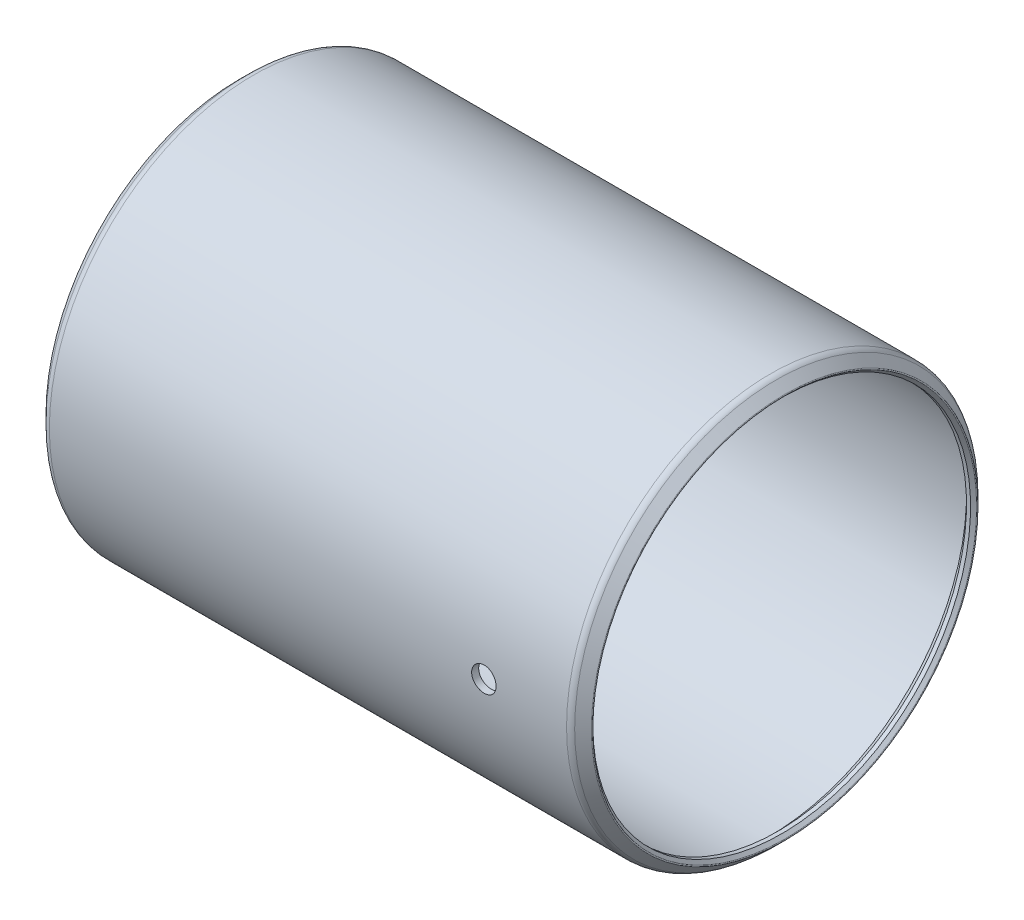
SolidWorks part; units mm, degrees
material "Cast Alloy Steel"
ref_plane "Front Plane" through (0, 0, 0) normal (0, 0, 1) x (1, 0, 0)
ref_plane "Top Plane" through (0, 0, 0) normal (0, 1, 0) x (1, 0, 0)
ref_plane "Right Plane" through (0, 0, 0) normal (1, 0, 0) x (0, 0, -1)
ref_plane "Plane1" through (68.961, 0, 0) normal (1, 0, 0) x (0, 0, -1)
sketch "Sketch1" plane through (0, 0, 0) normal (0, 0, 1) x (1, 0, 0)
  line L0 (-0.9191, 24.9094) -> (-0.5271, 24.5174)
  line L1 (-0.5271, 24.5174) -> (0, 24.5174)
  line L2 (0, 24.5174) -> (1.0541, 25.5714)
  line L3 (1.0541, 25.5714) -> (67.9069, 25.5714)
  line L4 (67.9069, 25.5714) -> (68.961, 24.5174)
  line L5 (68.961, 24.5174) -> (69.4881, 24.5174)
  line L6 (69.4881, 24.5174) -> (69.8801, 24.9094)
  line L7 (69.8801, 25.089) -> (68.792, 26.1771)
  line L8 (68.0466, 26.4858) -> (0.9144, 26.4858)
  line L9 (0.169, 26.1771) -> (-0.9191, 25.089)
  line L10 (68.961, 0) -> (0, 0) construction
  arc A0 (-0.9191, 25.089) -> (-0.9191, 24.9094) centre (-0.8293, 24.9992) ccw
  arc A1 (69.8801, 24.9094) -> (69.8801, 25.089) centre (69.7903, 24.9992) ccw
  arc A2 (68.792, 26.1771) -> (68.0466, 26.4858) centre (68.0466, 25.4317) ccw
  arc A3 (0.9144, 26.4858) -> (0.169, 26.1771) centre (0.9144, 25.4317) ccw
revolve "Revolve1" add sketch "Sketch1" angle 360 about L10 reverse direction yes
sketch "Sketch2" plane through (0, 0, 0) normal (0, 0, 1) x (1, 0, 0)
  circle A0 centre (57.3151, 0) radius 1.5875
extrude "Cut-Extrude1" cut sketch "Sketch2" along normal blind 26.4858
ref_plane "Plane2" through (34.4805, 0, 0) normal (1, 0, 0) x (0, 0, -1)
ref_plane "cp1 XY" through (34.4805, 0, 0) normal (1, 0, 0) x (0, 0, -1)
ref_plane "cp1 XZ" through (0, 26.4858, 0) normal (0, -1, 0) x (-1, 0, 0)
ref_plane "cp1 YZ" through (0, 0, 0) normal (0, 0, -1) x (-1, 0, 0)
ref_axis "cp1 X" through (34.4805, 26.4858, 80.9) along (0, 0, -1)
ref_axis "cp1 Y" through (34.4805, -50, 0) along (0, 1, 0)
ref_axis "cp1 Z" through (80.9, 26.4858, 0) along (-1, 0, 0)
sketch3d "cp1"
  point P0 (34.4805, 26.4858, 0)
ref_plane "cp2 XY" through (34.4805, 0, 0) normal (1, 0, 0) x (0, 0, -1)
ref_plane "cp2 XZ" through (0, 0, 0) normal (0, -1, 0) x (-1, 0, 0)
ref_plane "cp2 YZ" through (0, 0, -26.4858) normal (0, 0, -1) x (-1, 0, 0)
ref_axis "cp2 X" through (34.4805, 0, 80.9) along (0, 0, -1)
ref_axis "cp2 Y" through (34.4805, -50, -26.4858) along (0, 1, 0)
ref_axis "cp2 Z" through (80.9, 0, -26.4858) along (-1, 0, 0)
sketch3d "cp2"
  point P0 (34.4805, 0, -26.4858)
ref_plane "cp3 XY" through (34.4805, 0, 0) normal (1, 0, 0) x (0, 0, -1)
ref_plane "cp3 XZ" through (0, -26.4858, 0) normal (0, -1, 0) x (-1, 0, 0)
ref_plane "cp3 YZ" through (0, 0, 0) normal (0, 0, -1) x (-1, 0, 0)
ref_axis "cp3 X" through (34.4805, -26.4858, 80.9) along (0, 0, -1)
ref_axis "cp3 Y" through (34.4805, -50, 0) along (0, 1, 0)
ref_axis "cp3 Z" through (80.9, -26.4858, 0) along (-1, 0, 0)
sketch3d "cp3"
  point P0 (34.4805, -26.4858, 0)
ref_plane "cp4 XY" through (34.4805, 0, 0) normal (1, 0, 0) x (0, 0, -1)
ref_plane "cp4 XZ" through (0, 0, 0) normal (0, -1, 0) x (-1, 0, 0)
ref_plane "cp4 YZ" through (0, 0, 26.4858) normal (0, 0, -1) x (-1, 0, 0)
ref_axis "cp4 X" through (34.4805, 0, 80.9) along (0, 0, -1)
ref_axis "cp4 Y" through (34.4805, -50, 26.4858) along (0, 1, 0)
ref_axis "cp4 Z" through (80.9, 0, 26.4858) along (-1, 0, 0)
sketch3d "cp4"
  point P0 (34.4805, 0, 26.4858)
ref_plane "tube_front XY" through (0, 0, 0) normal (1, 0, 0) x (0, 0, -1)
ref_plane "tube_front XZ" through (0, 0, 0) normal (0, -1, 0) x (-1, 0, 0)
ref_plane "tube_front YZ" through (0, 0, 0) normal (0, 0, -1) x (-1, 0, 0)
ref_axis "tube_front X" through (0, 0, 80.9) along (0, 0, -1)
ref_axis "tube_front Y" through (0, -50, 0) along (0, 1, 0)
ref_axis "tube_front Z" through (80.9, 0, 0) along (-1, 0, 0)
sketch3d "tube_front"
  point P0 (0, 0, 0)
ref_plane "tube_rear XY" through (68.961, 0, 0) normal (1, 0, 0) x (0, 0, -1)
ref_plane "tube_rear XZ" through (0, 0, 0) normal (0, -1, 0) x (-1, 0, 0)
ref_plane "tube_rear YZ" through (0, 0, 0) normal (0, 0, -1) x (-1, 0, 0)
ref_axis "tube_rear X" through (68.961, 0, 80.9) along (0, 0, -1)
ref_axis "tube_rear Y" through (68.961, -50, 0) along (0, 1, 0)
ref_axis "tube_rear Z" through (80.9, 0, 0) along (-1, 0, 0)
sketch3d "tube_rear"
  point P0 (68.961, 0, 0)
